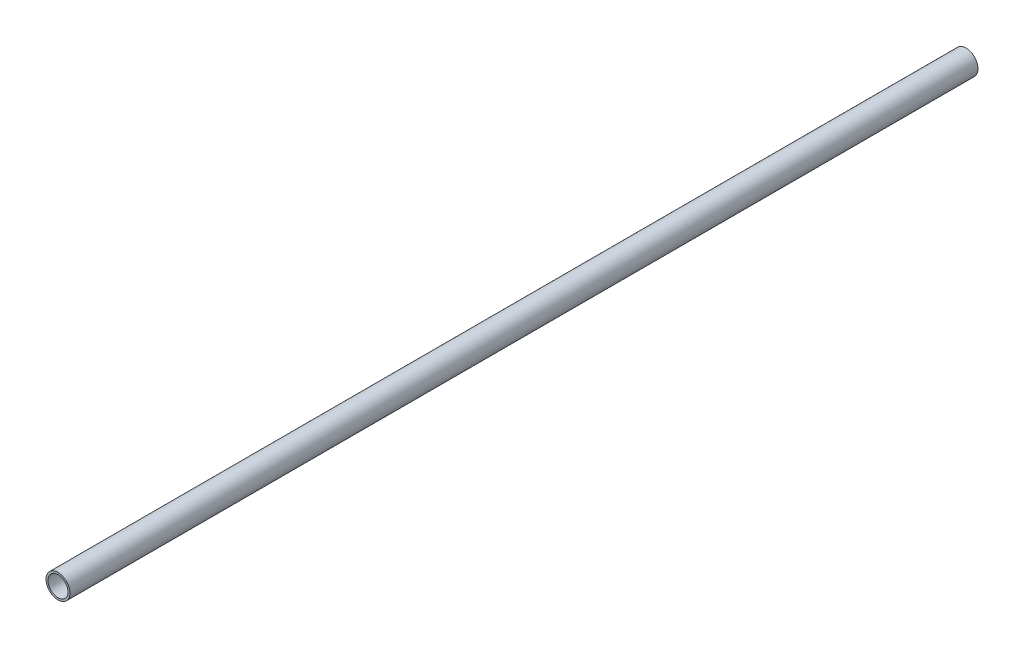
SolidWorks part; units mm, degrees
material "PVC Rigid"
ref_plane "Front Plane" through (0, 0, 0) normal (0, 0, 1) x (1, 0, 0)
ref_plane "Top Plane" through (0, 0, 0) normal (0, 1, 0) x (1, 0, 0)
ref_plane "Right Plane" through (0, 0, 0) normal (1, 0, 0) x (0, 0, -1)
sketch "Sketch1" plane through (0, 0, 0) normal (0, 0, 1) x (1, 0, 0)
  circle A0 centre (0, 0) radius 20.193
  circle A1 centre (0, 0) radius 24.13
  dimension "D1" = 48.26
  dimension "D2" = 40.386
extrude "Boss-Extrude1" add sketch "Sketch1" along normal blind 1828.8
ref_axis "Axis1" through (0, 0, 1828.8) along (0, 0, -1)
